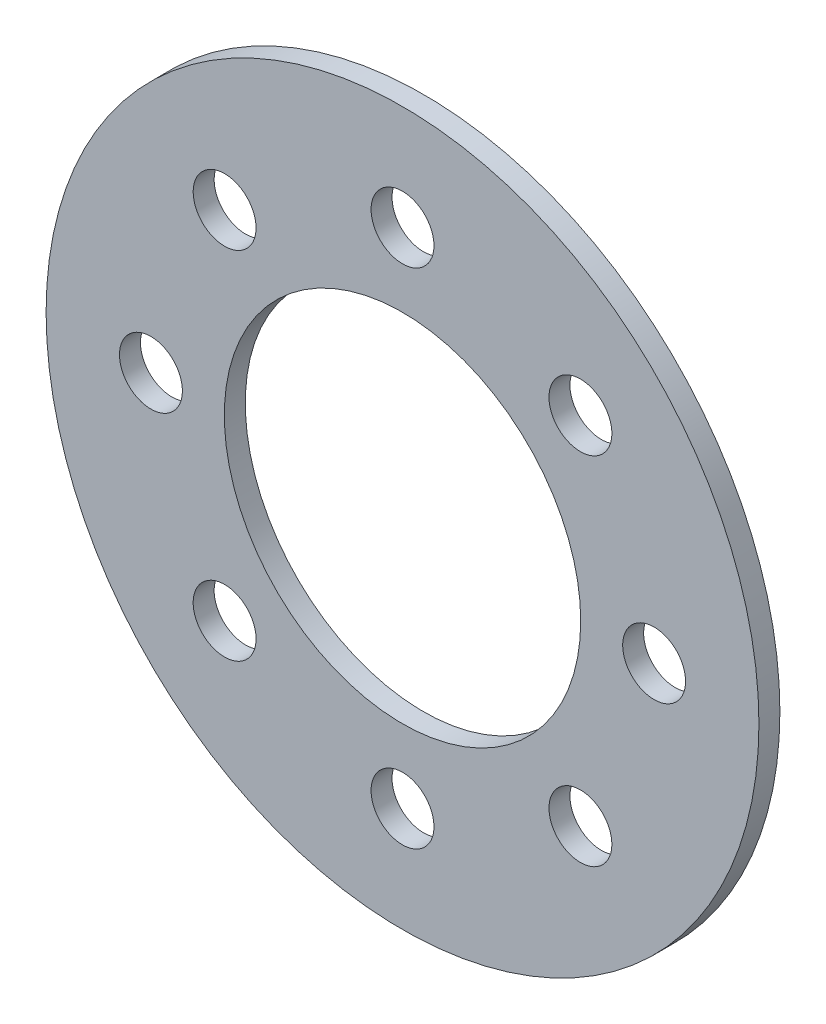
SolidWorks part; units mm, degrees
material "PLA 50%"
ref_plane "Front Plane" through (0, 0, 0) normal (0, 0, 1) x (1, 0, 0)
ref_plane "Top Plane" through (0, 0, 0) normal (0, 1, 0) x (1, 0, 0)
ref_plane "Right Plane" through (0, 0, 0) normal (1, 0, 0) x (0, 0, -1)
ref_axis "X" through (-88.99, 0, 0) along (1, 0, 0)
ref_axis "Y" through (0, 55, 0) along (0, -1, 0)
ref_axis "Z" through (0, 0, -88.99) along (0, 0, 1)
sketch "Sketch1" plane through (0, 0, 0) normal (0, 0, 1) x (1, 0, 0)
  circle A0 centre (0, 0) radius 8.5
  circle A1 centre (0, 0) radius 17
  dimension "D1" = 34
  dimension "D2" = 17
extrude "Boss-Extrude1" add sketch "Sketch1" along normal blind 1
sketch "Sketch2" plane through (0, 0, 1) normal (0, 0, 1) x (1, 0, 0)
  circle A0 centre (0, 12) radius 1.5
  point P2 (0, 0)
  dimension "D1" = 3
  dimension "D2" = 12
extrude "Cut-Extrude1" cut sketch "Sketch2" against normal through all both
pattern_circular "CirPattern1" count 8 over 360 about axis through (0, 0, 1) along (0, 0, -1) of "Cut-Extrude1"
